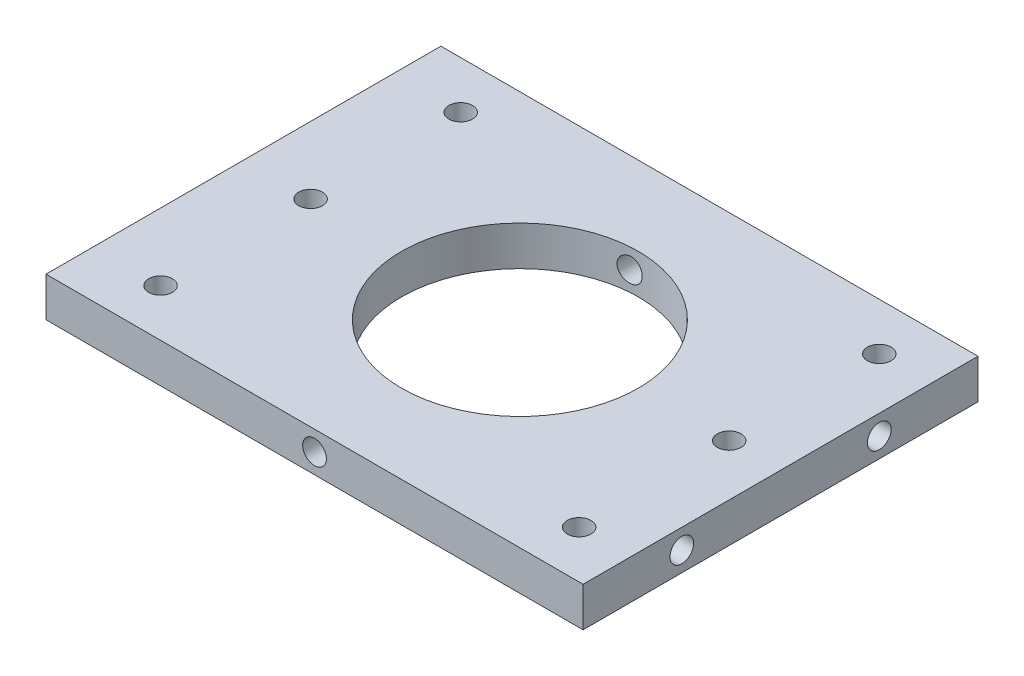
SolidWorks part; units mm, degrees
ref_plane "Plan de face" through (0, 0, 0) normal (0, 0, 1) x (1, 0, 0)
ref_plane "Plan de dessus" through (0, 0, 0) normal (0, 1, 0) x (1, 0, 0)
ref_plane "Plan de droite" through (0, 0, 0) normal (1, 0, 0) x (0, 0, -1)
sketch "Esquisse1" plane through (0, 0, 0) normal (0, 0, 1) x (1, 0, 0)
  line L0 (-15.5, -47.5) -> (52.5, -47.5) construction
  line L5 (-15.5, -45) -> (52.5, -45)
  line L6 (-15.5, -45) -> (-15.5, -50)
  line L7 (-15.5, -50) -> (52.5, -50)
  line L8 (52.5, -45) -> (52.5, -50)
  line L9 (18.5, -45) -> (18.5, -50) construction
  dimension "D1" = 5
  dimension "D2" = 68
extrude "Boss.-Extru.1" add sketch "Esquisse1" along normal blind 50 contours L5 | L7 L8 L5 L6
sketch "Esquisse2" plane through (0, -45, 0) normal (0, 1, 0) x (-1, 0, 0)
  line L0 (15.5, 50) -> (-52.5, 50) construction
  line L1 (15.5, 0) -> (-52.5, 0) construction
  line L7 (-52.5, 50) -> (-52.5, 0) construction
  circle A0 centre (-19.5, 25) radius 15
  circle A1 centre (-46, 44) radius 1.5
  circle A2 centre (-46, 6) radius 1.5
  circle A3 centre (7, 44) radius 1.5
  circle A4 centre (7, 6) radius 1.5
  circle A6 centre (7, 25) radius 1.5
  circle A7 centre (-46, 25) radius 1.5
  dimension "D6" = 6
  dimension "D2" = 53
  dimension "D3" = 53
  dimension "D4" = 26.5
  dimension "D5" = 26.5
  dimension "D7" = 6
  dimension "D8" = 6
  dimension "D9" = 6
  dimension "D10" = 33
  dimension "D11" = 25
  dimension "D12" = 25
  dimension "D13" = 25
extrude "Enlèv. mat.-Extru.1" cut sketch "Esquisse2" against normal through all
sketch "Esquisse3" plane through (-15.5, 0, 0) normal (-1, 0, 0) x (0, 0, 1)
  line L0 (50, -50) -> (0, -50) construction
  line L1 (0, -45) -> (0, -50) construction
  line L2 (50, -45) -> (50, -50) construction
  circle A0 centre (12.5, -47.5) radius 1.5
  circle A1 centre (37.5, -47.5) radius 1.5
  dimension "D1" = 2.5
  dimension "D2" = 2.5
  dimension "D3" = 12.5
  dimension "D4" = 12.5
extrude "Enlèv. mat.-Extru.2" cut sketch "Esquisse3" against normal blind 10
sketch "Esquisse4" plane through (52.5, 0, 0) normal (1, 0, 0) x (0, 0, -1)
  line L0 (-50, -50) -> (0, -50) construction
  line L1 (-50, -45) -> (-50, -50) construction
  line L2 (0, -45) -> (0, -50) construction
  circle A0 centre (-37.5, -47.5) radius 1.5
  circle A1 centre (-12.5, -47.5) radius 1.5
  dimension "D1" = 2.5
  dimension "D2" = 2.5
  dimension "D3" = 12.5
  dimension "D4" = 12.5
extrude "Enlèv. mat.-Extru.3" cut sketch "Esquisse4" against normal blind 10
sketch "Esquisse5" plane through (0, 0, 50) normal (0, 0, 1) x (1, 0, 0)
  line L0 (-15.5, -45) -> (-15.5, -50) construction
  line L1 (-15.5, -50) -> (52.5, -50) construction
  circle A0 centre (18.5, -47.5) radius 1.5
  dimension "D1" = 34
  dimension "D2" = 2.5
extrude "Enlèv. mat.-Extru.4" cut sketch "Esquisse5" against normal through all contours A0
